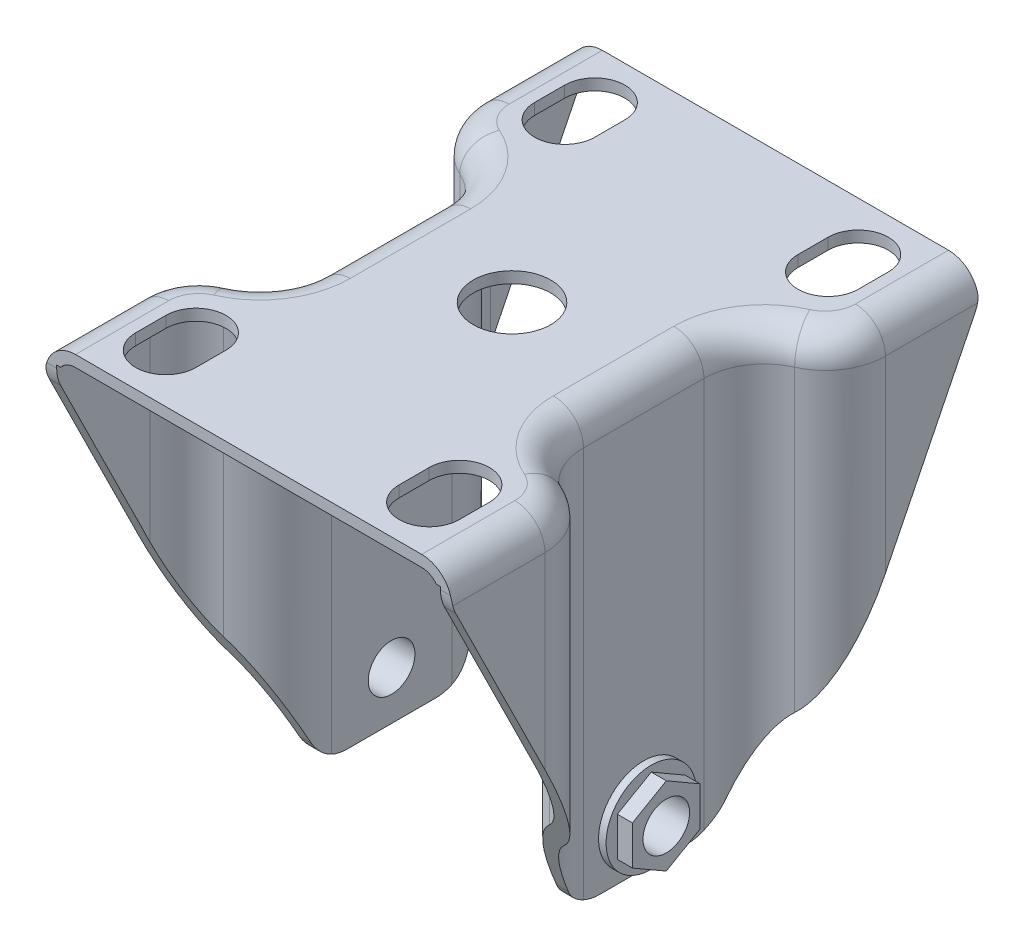
SolidWorks part; units mm, degrees
ref_plane "Front Plane" through (0, 0, 0) normal (0, 0, 1) x (1, 0, 0)
ref_plane "Top Plane" through (0, 0, 0) normal (0, 1, 0) x (1, 0, 0)
ref_plane "Right Plane" through (0, 0, 0) normal (1, 0, 0) x (0, 0, -1)
sketch "Sketch1" plane through (0, 0, 0) normal (1, 0, 0) x (0, 0, -1)
  line L0 (0, 0) -> (0, 50) construction
  line L1 (0, 0) -> (0, -6) construction
  line L2 (-35, 50) -> (-35, 46)
  line L5 (5.8977, -6.4596) -> (-5.8977, -6.4596)
  line L9 (-35, 50) -> (35, 50)
  line L10 (-35, 46) -> (-10.3776, -3.68)
  line L11 (35, 50) -> (35, 46)
  line L12 (35, 46) -> (10.3776, -3.68)
  circle A0 centre (0, 0) radius 3.1
  arc A1 (10.3776, -3.68) -> (5.8977, -6.4596) centre (5.8977, -1.4596) cw
  arc A2 (-5.8977, -6.4596) -> (-10.3776, -3.68) centre (-5.8977, -1.4596) cw
  point P4 (0, 19.4165)
  dimension "D1" = 6.2
  dimension "D2" = 6
  dimension "D8" = 5
  dimension "D3" = 56
  dimension "D4" = 4
  dimension "D5" = 35
  dimension "D6" = 35
  dimension "D7" = 4
extrude "Boss-Extrude1" add sketch "Sketch1" along normal blind 27 and the other way blind 27
sketch "Sketch2" plane through (0, 50, 0) normal (0, 1, 0) x (1, 0, 0)
  line L1 (-27, -16) -> (27, -16)
  line L2 (-17.5, -16) -> (-17.5, 16)
  line L3 (-27, 16) -> (27, 16)
  line L4 (-27, -35) -> (27, -35)
  line L5 (27, -35) -> (27, 35)
  line L6 (27, 35) -> (-27, 35)
  line L7 (-27, 35) -> (-27, -35)
  line L8 (-27, -35) -> (27, -35)
  line L9 (27, -35) -> (27, 35)
  line L10 (27, 35) -> (-27, 35)
  line L11 (-27, 35) -> (-27, -35)
  line L12 (17.5, -16) -> (17.5, 16)
  line L13 (-17.5, -16) -> (17.5, 16) construction
  line L14 (-17.5, 16) -> (17.5, -16) construction
  point P2 (0, 0)
  line M6 (27, -35) -> (27, 35)
  line M8 (-27, 35) -> (-27, -35)
  dimension "D2" = 35
  dimension "D3" = 19
  dimension "D1" = 0
extrude "Cut-Extrude1" cut sketch "Sketch2" against normal through all contours L3 L1 L2 M8 | L12 L1 L3 M6 region at (-22.25, 50, 0) region at (22.25, 50, 0)
fillet "Fillet1" radius 8 4 edges at (-17.5, 28.8321, -16) (-17.5, 28.8321, 16) (17.5, 28.8321, 16) (17.5, 28.8321, -16)
fillet "Fillet2" radius 8 4 edges at (-27, 28.8321, 16) (-27, 28.8321, -16) (27, 28.8321, 16) (27, 28.8321, -16)
fillet "Fillet3" radius 4 14 edges at (27, 50, -28.8101) (25.7082, 50, -18.2613) (18.7918, 50, -12.3589) (17.5, 50, 0) (18.7918, 50, 12.3589) (25.7082, 50, 18.2613) (-27, 50, -28.8101) (-25.7082, 50, -18.2613) (-18.7918, 50, -12.3589) (-17.5, 50, 0) (-18.7918, 50, 12.3589) (-25.7082, 50, 18.2613) (27, 50, 28.8101) (-27, 50, 28.8101)
shell "Shell1" thickness 1.5
sketch "Sketch3" plane through (0, -6.4596, 0) normal (0, -1, 0) x (1, 0, 0)
  line L0 (-25.5, 33.3259) -> (-25.5, 22.6202) construction
  line L1 (-25.5, 38.1797) -> (-25.5, 22.6202)
  line L2 (-16, 5.8977) -> (-16, 8) construction
  line L3 (-16, 5.8977) -> (-16, 8)
  line L4 (-16, 5.8977) -> (-16, -5.8977) construction
  line L5 (-16, 5.8977) -> (-16, -5.8977)
  line L6 (-16, -8) -> (-16, -5.8977) construction
  line L7 (-16, -8) -> (-16, -5.8977)
  line L8 (-25.5, -22.6202) -> (-25.5, -33.3259) construction
  line L9 (-25.5, -22.6202) -> (-25.5, -38.5493)
  line L10 (25.5, -22.6202) -> (25.5, -33.3259) construction
  line L11 (25.5, -22.6202) -> (25.5, -38.5493)
  line L12 (16, -5.8977) -> (16, -8) construction
  line L13 (16, -5.8977) -> (16, -8)
  line L14 (16, 5.8977) -> (16, -5.8977) construction
  line L15 (16, 5.8977) -> (16, -5.8977)
  line L16 (16, 8) -> (16, 5.8977) construction
  line L17 (16, 8) -> (16, 5.8977)
  line L18 (25.5, 33.3259) -> (25.5, 22.6202) construction
  line L19 (25.5, 38.1797) -> (25.5, 22.6202)
  line L20 (-25.5, 38.1797) -> (25.5, 38.1797)
  line L21 (-25.5, -38.5493) -> (25.5, -38.5493)
  arc A0 (-25.5, 22.6202) -> (-21.6406, 16.6807) centre (-19, 22.6202) ccw construction
  arc A1 (-25.5, 22.6202) -> (-21.6406, 16.6807) centre (-19, 22.6202) ccw
  arc A2 (-16.0564, 9.0337) -> (-21.6406, 16.6807) centre (-25.5, 8) ccw construction
  arc A3 (-16.0564, 9.0337) -> (-21.6406, 16.6807) centre (-25.5, 8) ccw
  arc A4 (-16, 8) -> (-16.0564, 9.0337) centre (-25.5, 8) ccw construction
  arc A5 (-16, 8) -> (-16.0564, 9.0337) centre (-25.5, 8) ccw
  arc A6 (-16.0564, -9.0337) -> (-16, -8) centre (-25.5, -8) ccw construction
  arc A7 (-16.0564, -9.0337) -> (-16, -8) centre (-25.5, -8) ccw
  arc A8 (-21.6406, -16.6807) -> (-16.0564, -9.0337) centre (-25.5, -8) ccw construction
  arc A9 (-21.6406, -16.6807) -> (-16.0564, -9.0337) centre (-25.5, -8) ccw
  arc A10 (-21.6406, -16.6807) -> (-25.5, -22.6202) centre (-19, -22.6202) ccw construction
  arc A11 (-21.6406, -16.6807) -> (-25.5, -22.6202) centre (-19, -22.6202) ccw
  arc A12 (25.5, -22.6202) -> (21.6406, -16.6807) centre (19, -22.6202) ccw construction
  arc A13 (25.5, -22.6202) -> (21.6406, -16.6807) centre (19, -22.6202) ccw
  arc A14 (16.0564, -9.0337) -> (21.6406, -16.6807) centre (25.5, -8) ccw construction
  arc A15 (16.0564, -9.0337) -> (21.6406, -16.6807) centre (25.5, -8) ccw
  arc A16 (16, -8) -> (16.0564, -9.0337) centre (25.5, -8) ccw construction
  arc A17 (16, -8) -> (16.0564, -9.0337) centre (25.5, -8) ccw
  arc A18 (16.0564, 9.0337) -> (16, 8) centre (25.5, 8) ccw construction
  arc A19 (16.0564, 9.0337) -> (16, 8) centre (25.5, 8) ccw
  arc A20 (21.6406, 16.6807) -> (16.0564, 9.0337) centre (25.5, 8) ccw construction
  arc A21 (21.6406, 16.6807) -> (16.0564, 9.0337) centre (25.5, 8) ccw
  arc A22 (21.6406, 16.6807) -> (25.5, 22.6202) centre (19, 22.6202) ccw construction
  arc A23 (21.6406, 16.6807) -> (25.5, 22.6202) centre (19, 22.6202) ccw
extrude "Cut-Extrude2" cut sketch "Sketch3" against normal blind 54
sketch "Sketch4" plane through (0, 0, 33.5) normal (0, 0, -1) x (-1, 0, 0)
  line L4 (-24.9691, 47.5404) -> (24.9691, 47.5404)
  line L6 (23, 48.5) -> (-23, 48.5)
  line L8 (-24.9691, 47.5404) -> (24.9691, 47.5404)
  line L10 (23, 48.5) -> (-23, 48.5)
  arc A2 (24.9691, 47.5404) -> (23, 48.5) centre (23, 46) ccw
  arc A3 (-23, 48.5) -> (-24.9691, 47.5404) centre (-23, 46) ccw
  arc A4 (24.9691, 47.5404) -> (23, 48.5) centre (23, 46) ccw
  arc A5 (-23, 48.5) -> (-24.9691, 47.5404) centre (-23, 46) ccw
  dimension "D1" = 0
extrude "Cut-Extrude3" cut sketch "Sketch4" against normal blind 54
sketch "Sketch5" plane through (0, 0, -33.5) normal (0, 0, 1) x (1, 0, 0)
  line L4 (-24.9691, 47.5404) -> (24.9691, 47.5404)
  line L6 (23, 48.5) -> (-23, 48.5)
  line L8 (-24.9691, 47.5404) -> (24.9691, 47.5404)
  line L10 (23, 48.5) -> (-23, 48.5)
  arc A2 (24.9691, 47.5404) -> (23, 48.5) centre (23, 46) ccw
  arc A3 (-23, 48.5) -> (-24.9691, 47.5404) centre (-23, 46) ccw
  arc A4 (24.9691, 47.5404) -> (23, 48.5) centre (23, 46) ccw
  arc A5 (-23, 48.5) -> (-24.9691, 47.5404) centre (-23, 46) ccw
  dimension "D1" = 0
extrude "Cut-Extrude4" cut sketch "Sketch5" against normal blind 54
fillet "Fillet4" radius 5 4 edges at (-26.25, 46, -35) (26.25, 46, -35) (26.25, 46, 35) (-26.25, 46, 35)
sketch "Sketch6" plane through (17.5, 0, 0) normal (1, 0, 0) x (0, 0, -1)
  circle A0 centre (0, 0) radius 6
  circle A1 centre (0, 0) radius 3.1
  dimension "D1" = 12
extrude "Boss-Extrude2" add sketch "Sketch6" along normal blind 1
mirror "Mirror1" about plane through (0, 0, 0) normal (1, 0, 0) of "Boss-Extrude2"
sketch "Sketch7" plane through (18.5, 0, 0) normal (1, 0, 0) x (0, 0, -1)
  line L1 (0, 5.1962) -> (-4.5, 2.5981)
  line L2 (-4.5, 2.5981) -> (-4.5, -2.5981)
  line L3 (-4.5, -2.5981) -> (0, -5.1962)
  line L4 (0, -5.1962) -> (4.5, -2.5981)
  line L5 (4.5, -2.5981) -> (4.5, 2.5981)
  line L6 (4.5, 2.5981) -> (0, 5.1962)
  circle A0 centre (0, 0) radius 4.5 construction
  circle A1 centre (0, 0) radius 3.1
  dimension "D1" = 9
extrude "Boss-Extrude3" add sketch "Sketch7" along normal blind 2
mirror "Mirror2" about plane through (0, 0, 0) normal (1, 0, 0) of "Boss-Extrude3"
sketch "Sketch8" plane through (0, 50, 0) normal (0, 1, 0) x (1, 0, 0)
  line L0 (-17.5, 24.5) -> (-17.5, 28.5) construction
  line L1 (-17.5, -26.5) -> (17.5, -26.5) construction
  line L2 (-17.5, -26.5) -> (-17.5, 26.5) construction
  line L3 (-17.5, 26.5) -> (17.5, 26.5) construction
  line L4 (17.5, -26.5) -> (17.5, 26.5) construction
  line L5 (-17.5, -26.5) -> (17.5, 26.5) construction
  line L6 (-17.5, 26.5) -> (17.5, -26.5) construction
  line L7 (-21.5, 24.5) -> (-21.5, 28.5)
  line L8 (-13.5, 24.5) -> (-13.5, 28.5)
  line L9 (17.5, 24.5) -> (17.5, 28.5) construction
  line L10 (13.5, 24.5) -> (13.5, 28.5)
  line L11 (21.5, 24.5) -> (21.5, 28.5)
  arc A0 (-21.5, 24.5) -> (-13.5, 24.5) centre (-17.5, 24.5) ccw
  arc A1 (-13.5, 28.5) -> (-21.5, 28.5) centre (-17.5, 28.5) ccw
  arc A2 (13.5, 24.5) -> (21.5, 24.5) centre (17.5, 24.5) ccw
  arc A3 (21.5, 28.5) -> (13.5, 28.5) centre (17.5, 28.5) ccw
  point P0 (0, 0)
  point P8 (-17.5, 26.5)
  point P14 (17.5, 26.5)
  dimension "D3" = 4
  dimension "D5" = 4
  dimension "D6" = 4
  dimension "D1" = 35
  dimension "D2" = 53
  dimension "D4" = 4
extrude "Cut-Extrude5" cut sketch "Sketch8" against normal blind 2
mirror "Mirror3" about plane through (0, 0, 0) normal (0, 0, 1) of "Cut-Extrude5"
sketch "Sketch9" plane through (0, 50, 0) normal (0, 1, 0) x (1, 0, 0)
  circle A0 centre (0, 0) radius 5.15
  dimension "D1" = 10.3
extrude "Cut-Extrude6" cut sketch "Sketch9" against normal blind 2
